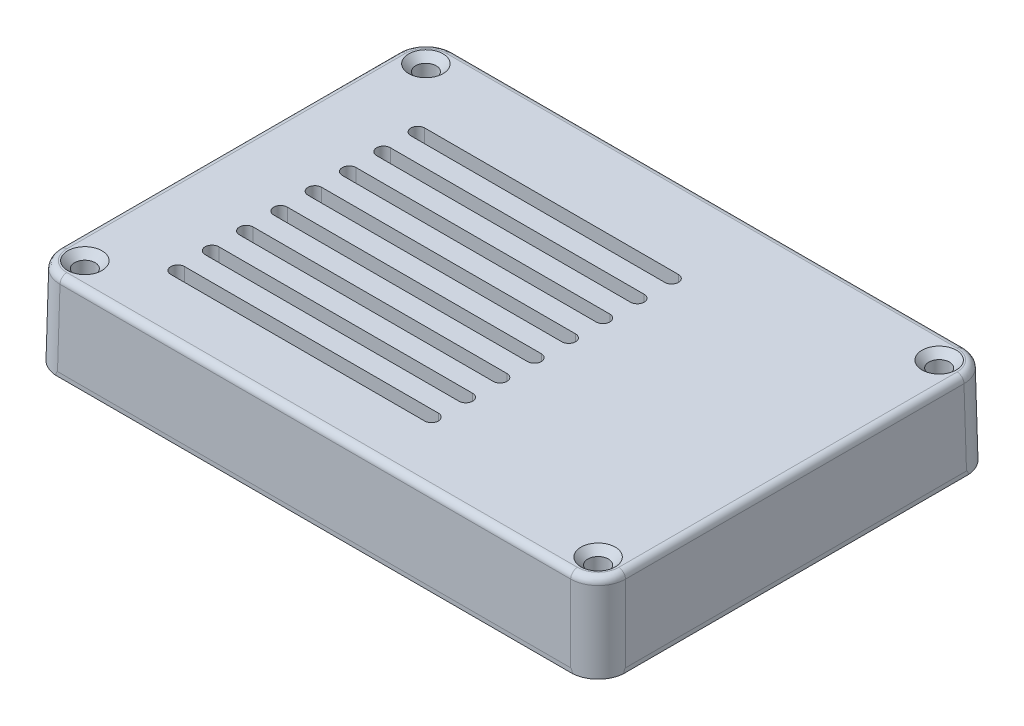
SolidWorks part; units mm, degrees
material "ABS PC"
ref_plane "Front Plane" through (0, 0, 0) normal (0, 0, 1) x (1, 0, 0)
ref_plane "Top Plane" through (0, 0, 0) normal (0, 1, 0) x (1, 0, 0)
ref_plane "Right Plane" through (0, 0, 0) normal (1, 0, 0) x (0, 0, -1)
sketch "Sketch1" plane through (0, 0, 0) normal (0, 1, 0) x (1, 0, 0)
  line L1 (-108.7297, 31.1354) -> (-25.9297, 31.1354)
  line L2 (-108.7297, 31.1354) -> (-108.7297, -26.5646)
  line L3 (-108.7297, -26.5646) -> (-25.9297, -26.5646)
  line L4 (-25.9297, 31.1354) -> (-25.9297, -26.5646)
  line L5 (-108.7297, 31.1354) -> (-25.9297, -26.5646) construction
  line L6 (-108.7297, -26.5646) -> (-25.9297, 31.1354) construction
  point P0 (-67.3297, 2.2854)
extrude "Boss-Extrude1" add sketch "Sketch1" along normal blind 12.6
chamfer "Chamfer1" distance 12 distance2 0.2 4 edges at (-25.9297, 12.6, -2.2854) (-67.3297, 12.6, -31.1354) (-108.7297, 12.6, -2.2854) (-67.3297, 12.6, 26.5646) first distance on face at (-25.9297, 6.3, -2.2854) first distance on face at (-67.3297, 6.3, -31.1354) first distance on face at (-108.7297, 6.3, -2.2854) first distance on face at (-67.3297, 6.3, 26.5646)
fillet "Fillet1" radius 4 4 edges at (-108.6297, 6.6, -31.0354) (-26.0297, 6.6, -31.0354) (-26.0297, 6.6, 26.4646) (-108.6297, 6.6, 26.4646)
sketch "Sketch2" plane through (0, 0, 0) normal (0, -1, 0) x (1, 0, 0)
  circle A0 centre (-104.7391, 22.5741) radius 1.5
  circle A1 centre (-29.9202, 22.5741) radius 1.5
  circle A2 centre (-104.7391, -27.1448) radius 1.5
  circle A3 centre (-29.9202, -27.1448) radius 1.5
extrude "Cut-Extrude1" cut sketch "Sketch2" against normal blind 12.6
fillet "Fillet2" radius 1 8 edges at (-107.3583, 12.6, -29.764) (-67.3297, 12.6, -30.9354) (-27.301, 12.6, -29.764) (-26.1297, 12.6, -2.2854) (-27.301, 12.6, 25.1933) (-67.3297, 12.6, 26.3646) (-107.3583, 12.6, 25.1933) (-108.5297, 12.6, -2.2854)
chamfer "Chamfer2" distance 1 angle 45 4 edges at (-104.7391, 12.6, 21.0741) (-29.9202, 12.6, 21.0741) (-29.9202, 12.6, -28.6448) (-104.7391, 12.6, -28.6448)
sketch "Sketch3" plane through (0, 0, 0) normal (0, -1, 0) x (1, 0, 0)
  line L0 (-105.0229, 26.5646) -> (-29.6364, 26.5646) construction
  line L1 (-99.7651, 22.0646) -> (-34.8942, 22.0646)
  line L2 (-104.2297, 17.6001) -> (-104.2297, -22.1708)
  line L3 (-99.7651, -26.6354) -> (-34.8942, -26.6354)
  line L4 (-30.4297, 17.6001) -> (-30.4297, -22.1708)
  line L5 (-100.7693, 23.0646) -> (-33.89, 23.0646)
  line L6 (-29.4297, 18.6043) -> (-29.4297, -23.175)
  line L7 (-108.7297, -27.4286) -> (-108.7297, 22.8579) construction
  line L8 (-25.9297, 22.8579) -> (-25.9297, -27.4286) construction
  line L9 (-29.6364, -31.1354) -> (-105.0229, -31.1354) construction
  line L10 (-100.7693, -27.6354) -> (-33.89, -27.6354)
  line L11 (-105.2297, 18.6043) -> (-105.2297, -23.175)
  arc A0 (-104.2297, 17.6001) -> (-99.7651, 22.0646) centre (-104.7391, 22.5741) ccw
  arc A1 (-34.8942, 22.0646) -> (-30.4297, 17.6001) centre (-29.9202, 22.5741) ccw
  arc A2 (-30.4297, -22.1708) -> (-34.8942, -26.6354) centre (-29.9202, -27.1448) ccw
  arc A3 (-99.7651, -26.6354) -> (-104.2297, -22.1708) centre (-104.7391, -27.1448) ccw
  arc A4 (-33.89, 23.0646) -> (-29.4297, 18.6043) centre (-29.9202, 22.5741) ccw
  arc A5 (-29.4297, -23.175) -> (-33.89, -27.6354) centre (-29.9202, -27.1448) ccw
  arc A6 (-100.7693, -27.6354) -> (-105.2297, -23.175) centre (-104.7391, -27.1448) ccw
  arc A7 (-105.2297, 18.6043) -> (-100.7693, 23.0646) centre (-104.7391, 22.5741) ccw
  point P0 (-67.3297, -2.2854)
  dimension "D5" = 1
  dimension "D1" = 4.5
  dimension "D2" = 4.5
  dimension "D3" = 4.5
  dimension "D4" = 4.5
extrude "Cut-Extrude2" cut sketch "Sketch3" against normal blind 10.4 contours A0 L1 A1 L4 A2 L3 A3 L2
extrude "Cut-Extrude-Thin1" cut sketch "Sketch3<4>" against normal blind 1 thin contours L11 A6 L10 A5 L6 A4 L5 A7 thin type one direction wall 1
sketch "Sketch3<4>" plane through (0, 0, 0) normal (0, -1, 0) x (1, 0, 0) same geometry as "Sketch3"
sketch "Sketch4" plane through (0, 12.6, 0) normal (0, 1, 0) x (1, 0, 0)
  line L0 (-96.7297, 18.9519) -> (-59.7297, 18.9519)
  line L1 (-96.7297, 16.9519) -> (-59.7297, 16.9519)
  line L2 (-30.1127, 29.9519) -> (-104.5466, 29.9519) construction
  line L3 (-96.7297, 18.9519) -> (-96.7297, 16.9519) construction
  line L4 (-59.7297, 18.9519) -> (-59.7297, 16.9519) construction
  line L5 (-96.7297, 13.9519) -> (-59.7297, 13.9519)
  line L6 (-96.7297, 11.9519) -> (-59.7297, 11.9519)
  line L7 (-96.7297, 13.9519) -> (-96.7297, 11.9519) construction
  line L8 (-59.7297, 13.9519) -> (-59.7297, 11.9519) construction
  line L9 (-96.7297, 8.9519) -> (-59.7297, 8.9519)
  line L10 (-96.7297, 6.9519) -> (-59.7297, 6.9519)
  line L11 (-96.7297, 8.9519) -> (-96.7297, 6.9519) construction
  line L12 (-59.7297, 8.9519) -> (-59.7297, 6.9519) construction
  line L13 (-96.7297, 3.9519) -> (-59.7297, 3.9519)
  line L14 (-96.7297, 1.9519) -> (-59.7297, 1.9519)
  line L15 (-96.7297, 3.9519) -> (-96.7297, 1.9519) construction
  line L16 (-59.7297, 3.9519) -> (-59.7297, 1.9519) construction
  line L17 (-96.7297, -1.0481) -> (-59.7297, -1.0481)
  line L18 (-96.7297, -3.0481) -> (-59.7297, -3.0481)
  line L19 (-96.7297, -1.0481) -> (-96.7297, -3.0481) construction
  line L20 (-59.7297, -1.0481) -> (-59.7297, -3.0481) construction
  line L21 (-96.7297, -6.0481) -> (-59.7297, -6.0481)
  line L22 (-96.7297, -8.0481) -> (-59.7297, -8.0481)
  line L23 (-96.7297, -6.0481) -> (-96.7297, -8.0481) construction
  line L24 (-59.7297, -6.0481) -> (-59.7297, -8.0481) construction
  line L25 (-96.7297, -11.0481) -> (-59.7297, -11.0481)
  line L26 (-96.7297, -13.0481) -> (-59.7297, -13.0481)
  line L27 (-96.7297, -11.0481) -> (-96.7297, -13.0481) construction
  line L28 (-59.7297, -11.0481) -> (-59.7297, -13.0481) construction
  line L29 (-96.7297, -16.0481) -> (-59.7297, -16.0481)
  line L30 (-96.7297, -18.0481) -> (-59.7297, -18.0481)
  line L31 (-96.7297, -16.0481) -> (-96.7297, -18.0481) construction
  line L32 (-59.7297, -16.0481) -> (-59.7297, -18.0481) construction
  line L33 (-108.7297, -22.5652) -> (-108.7297, 27.1359) construction
  arc A0 (-96.7297, 18.9519) -> (-96.7297, 16.9519) centre (-96.7297, 17.9519) ccw
  arc A1 (-59.7297, 16.9519) -> (-59.7297, 18.9519) centre (-59.7297, 17.9519) ccw
  arc A2 (-96.7297, 13.9519) -> (-96.7297, 11.9519) centre (-96.7297, 12.9519) ccw
  arc A3 (-59.7297, 11.9519) -> (-59.7297, 13.9519) centre (-59.7297, 12.9519) ccw
  arc A4 (-96.7297, 8.9519) -> (-96.7297, 6.9519) centre (-96.7297, 7.9519) ccw
  arc A5 (-59.7297, 6.9519) -> (-59.7297, 8.9519) centre (-59.7297, 7.9519) ccw
  arc A6 (-96.7297, 3.9519) -> (-96.7297, 1.9519) centre (-96.7297, 2.9519) ccw
  arc A7 (-59.7297, 1.9519) -> (-59.7297, 3.9519) centre (-59.7297, 2.9519) ccw
  arc A8 (-96.7297, -1.0481) -> (-96.7297, -3.0481) centre (-96.7297, -2.0481) ccw
  arc A9 (-59.7297, -3.0481) -> (-59.7297, -1.0481) centre (-59.7297, -2.0481) ccw
  arc A10 (-96.7297, -6.0481) -> (-96.7297, -8.0481) centre (-96.7297, -7.0481) ccw
  arc A11 (-59.7297, -8.0481) -> (-59.7297, -6.0481) centre (-59.7297, -7.0481) ccw
  arc A12 (-96.7297, -11.0481) -> (-96.7297, -13.0481) centre (-96.7297, -12.0481) ccw
  arc A13 (-59.7297, -13.0481) -> (-59.7297, -11.0481) centre (-59.7297, -12.0481) ccw
  arc A14 (-96.7297, -16.0481) -> (-96.7297, -18.0481) centre (-96.7297, -17.0481) ccw
  arc A15 (-59.7297, -18.0481) -> (-59.7297, -16.0481) centre (-59.7297, -17.0481) ccw
  dimension "D4" = 37
  dimension "D5" = 12
  dimension "D1" = 2
  dimension "D2" = 11
  dimension "D3" = 8
extrude "Cut-Extrude3" cut sketch "Sketch4" against normal blind 10.4
